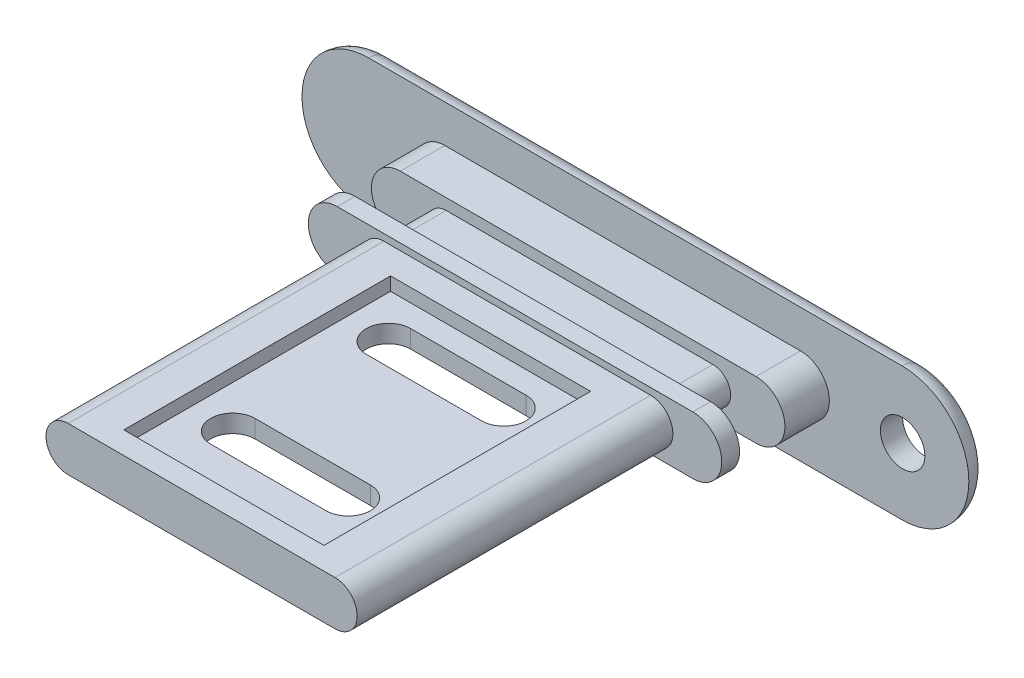
SolidWorks part; units mm, degrees
ref_plane "前视基准面" through (0, 0, 0) normal (0, 0, 1) x (1, 0, 0)
ref_plane "上视基准面" through (0, 0, 0) normal (0, 1, 0) x (1, 0, 0)
ref_plane "右视基准面" through (0, 0, 0) normal (1, 0, 0) x (0, 0, -1)
other "Configuration Table"
sketch "草图5" plane through (0, 0, 0) normal (0, 0, 1) x (1, 0, 0)
  line L0 (-5.7423, 0) -> (6.2577, 0) construction
  line L1 (-5.7423, 1.5) -> (6.2577, 1.5)
  line L2 (-5.7423, -1.5) -> (6.2577, -1.5)
  arc A0 (-5.7423, 1.5) -> (-5.7423, -1.5) centre (-5.7423, 0) ccw
  arc A1 (6.2577, -1.5) -> (6.2577, 1.5) centre (6.2577, 0) ccw
  point P3 (0.2577, 0)
  dimension "D2" = 1.5
  dimension "D1" = 12
extrude "凸台-拉伸2" add sketch "草图5" along normal blind 0.5
sketch "草图6" plane through (0, 0, 0) normal (0, 0, -1) x (-1, 0, 0)
  circle A0 centre (-6.2678, 0) radius 0.5
extrude "切除-拉伸1" cut sketch "草图6" against normal through all
sketch "草图7" plane through (0, 0, 0.5) normal (0, 0, 1) x (1, 0, 0)
  line L0 (3.9705, 0) -> (-4.0295, 0) construction
  line L1 (3.9705, -0.65) -> (-4.0295, -0.65)
  line L2 (3.9705, 0.65) -> (-4.0295, 0.65)
  arc A0 (3.9705, -0.65) -> (3.9705, 0.65) centre (3.9705, 0) ccw
  arc A1 (-4.0295, 0.65) -> (-4.0295, -0.65) centre (-4.0295, 0) ccw
  point P3 (-0.0295, 0)
  dimension "D2" = 0.65
  dimension "D1" = 8
extrude "凸台-拉伸3" add sketch "草图7" along normal blind 1
sketch "草图8" plane through (0, 0, 1.5) normal (0, 0, 1) x (1, 0, 0)
  line L0 (3, 0) -> (-3, 0) construction
  line L1 (3, -0.4) -> (-3, -0.4)
  line L2 (3, 0.4) -> (-3, 0.4)
  arc A0 (3, -0.4) -> (3, 0.4) centre (3, 0) ccw
  arc A1 (-3, 0.4) -> (-3, -0.4) centre (-3, 0) ccw
  point P3 (0, 0)
  dimension "D2" = 0.4
  dimension "D1" = 6
extrude "凸台-拉伸4" add sketch "草图8" along normal blind 1
sketch "草图9" plane through (0, 0, 2.5) normal (0, 0, 1) x (1, 0, 0)
  line L0 (-4.0505, 0) -> (3.9495, 0) construction
  line L1 (-4.0505, 0.65) -> (3.9495, 0.65)
  line L2 (-4.0505, -0.65) -> (3.9495, -0.65)
  arc A0 (-4.0505, 0.65) -> (-4.0505, -0.65) centre (-4.0505, 0) ccw
  arc A1 (3.9495, -0.65) -> (3.9495, 0.65) centre (3.9495, 0) ccw
  point P3 (-0.0505, 0)
  dimension "D2" = 0.65
  dimension "D1" = 8
extrude "凸台-拉伸5" add sketch "草图9" along normal blind 0.4
sketch "草图10" plane through (0, 0, 2.9) normal (0, 0, 1) x (1, 0, 0)
  line L0 (-3, 0) -> (3, 0) construction
  line L1 (-3, 0.5) -> (3, 0.5)
  line L2 (-3, -0.5) -> (3, -0.5)
  arc A0 (-3, 0.5) -> (-3, -0.5) centre (-3, 0) ccw
  arc A1 (3, -0.5) -> (3, 0.5) centre (3, 0) ccw
  point P3 (0, 0)
  dimension "D2" = 0.5
  dimension "D1" = 6
extrude "凸台-拉伸6" add sketch "草图10" along normal blind 7.1
sketch "草图11" plane through (0, -0.5, 0) normal (0, -1, 0) x (-1, 0, 0)
  line L1 (2.25, -9.5) -> (-2.25, -9.5)
  line L2 (2.25, -9.5) -> (2.25, -3.5)
  line L3 (2.25, -3.5) -> (-2.25, -3.5)
  line L4 (-2.25, -9.5) -> (-2.25, -3.5)
  line L5 (2.25, -9.5) -> (-2.25, -3.5) construction
  line L6 (2.25, -3.5) -> (-2.25, -9.5) construction
  point P0 (0, -6.5)
  dimension "D1" = 4.5
  dimension "D2" = 6
extrude "切除-拉伸2" cut sketch "草图11" against normal blind 0.3
sketch "草图13" plane through (0, 0.5, 0) normal (0, 1, 0) x (1, 0, 0)
  line L1 (-2.25, -3.5) -> (2.25, -3.5)
  line L2 (-2.25, -3.5) -> (-2.25, -9.5)
  line L3 (-2.25, -9.5) -> (2.25, -9.5)
  line L4 (2.25, -3.5) -> (2.25, -9.5)
  line L5 (-2.25, -3.5) -> (2.25, -9.5) construction
  line L6 (-2.25, -9.5) -> (2.25, -3.5) construction
  point P0 (0, -6.5)
  dimension "D1" = 6
  dimension "D2" = 4.5
extrude "切除-拉伸3" cut sketch "草图13" against normal blind 0.3
sketch "草图14" plane through (0, 0.2, 0) normal (0, 1, 0) x (1, 0, 0)
  line L0 (1.2978, -4.5) -> (-1.2978, -4.5) construction
  line L1 (1.2978, -5) -> (-1.2978, -5)
  line L2 (1.2978, -4) -> (-1.2978, -4)
  line L3 (1.2978, -8) -> (-1.2978, -8) construction
  line L4 (1.2978, -8.5) -> (-1.2978, -8.5)
  line L5 (1.2978, -7.5) -> (-1.2978, -7.5)
  arc A0 (1.2978, -5) -> (1.2978, -4) centre (1.2978, -4.5) ccw
  arc A1 (-1.2978, -4) -> (-1.2978, -5) centre (-1.2978, -4.5) ccw
  arc A2 (1.2978, -8.5) -> (1.2978, -7.5) centre (1.2978, -8) ccw
  arc A3 (-1.2978, -7.5) -> (-1.2978, -8.5) centre (-1.2978, -8) ccw
  point P2 (0, -4.5)
  point P7 (0, -8)
  dimension "D1" = 1
  dimension "D2" = 1
extrude "切除-拉伸4" cut sketch "草图14" against normal through all
fillet "圆角2" radius 0.5 4 edges at (-7.2423, 0, 0) (0.2577, 1.5, 0) (7.7577, 0, 0) (0.2577, -1.5, 0)
